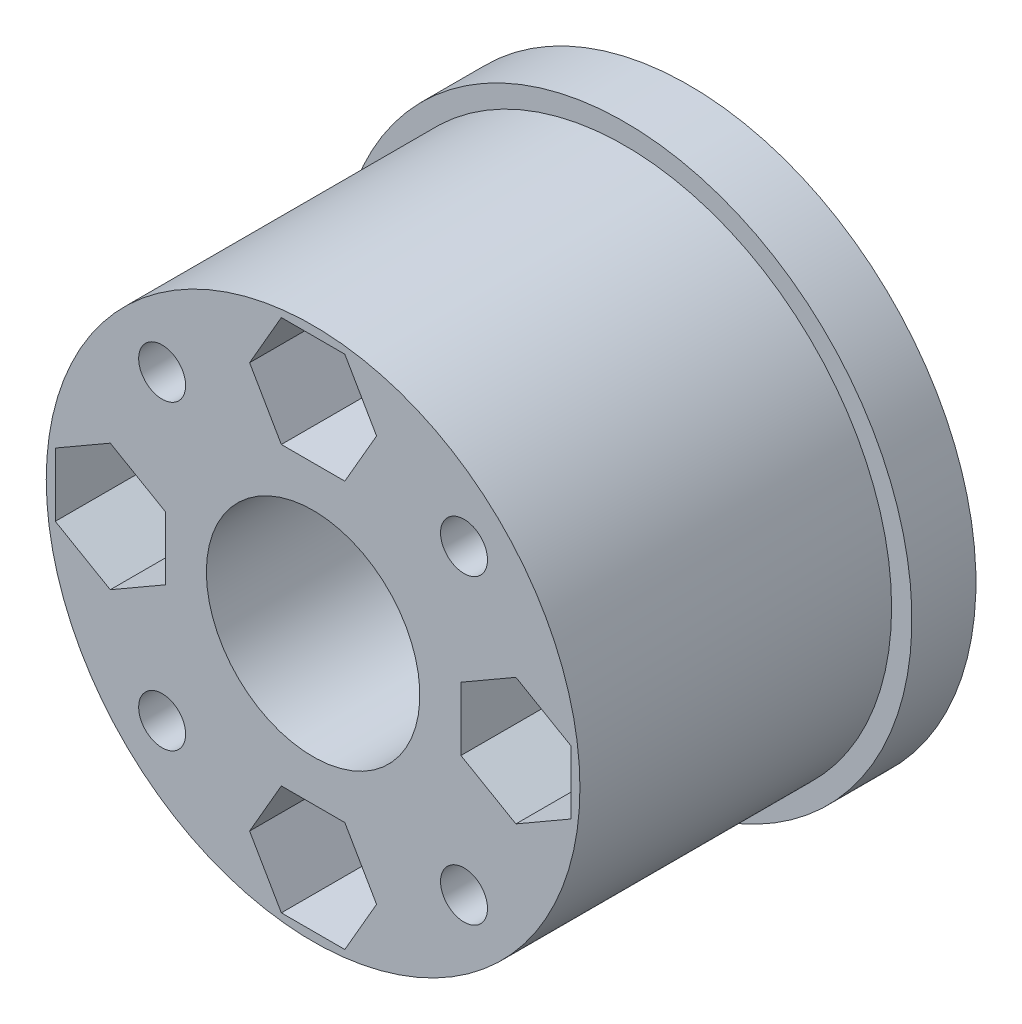
SolidWorks part; units mm, degrees
ref_plane "Front Plane" through (0, 0, 0) normal (0, 0, 1) x (1, 0, 0)
ref_plane "Top Plane" through (0, 0, 0) normal (0, 1, 0) x (1, 0, 0)
ref_plane "Right Plane" through (0, 0, 0) normal (1, 0, 0) x (0, 0, -1)
ref_axis "Z" through (0, 0, 15.48) along (0, 0, -1)
ref_plane "Plane1" through (0, 0, 0) normal (0.7071, 0.7071, 0) x (0, 0, -1)
sketch "Sketch10" plane through (0, 0, 0) normal (0, 1, 0) x (1, 0, 0)
  line L0 (-13.45, 3) -> (-7.5, 3)
  line L1 (0, 38.469) -> (0, 33.6342) construction
  line L2 (0, -15.48) -> (0, 3.88) construction
  line L3 (-13.45, 3) -> (-13.45, 0)
  line L4 (-13.45, 0) -> (-12.5, 0)
  line L5 (-12.5, 0) -> (-12.5, -14.6)
  line L10 (-12.5, -17.2) -> (-11, -17.2) construction
  line L11 (-11, -17.2) -> (-11, -16.2) construction
  line L12 (-11, -16.2) -> (-5, -16.2) construction
  line L14 (-7.5, 3) -> (-7.5, 2)
  line L15 (-7.5, 2) -> (-5, 2)
  line L18 (-5, 2) -> (-5, -14.6)
  line L19 (-12.5, -14.6) -> (-5, -14.6)
  line L20 (-5, -16.2) -> (-5, -14.6)
  line L21 (-12.5, -14.6) -> (-12.5, -17.2)
  dimension "D1" = 25
  dimension "D2" = 26.9
  dimension "D4" = 3
  dimension "D3" = 17.2
  dimension "D8" = 1
  dimension "D9" = 11
  dimension "D11" = 1
  dimension "D12" = 15
  dimension "D5" = 14.6
  dimension "D10" = 10
revolve "Revolve1" add sketch "Sketch10" angle 360 about L1
sketch "Sketch11" plane through (0, 0, 0) normal (0, 0, 1) x (1, 0, 0)
  line L0 (9.5, 0) -> (0, 0) construction
  circle A0 centre (9.5, 0) radius 1.325
  dimension "D2" = 2.65
  dimension "D1" = 9.5
extrude "AttachmentBoltHoles" cut sketch "Sketch11" against normal through all both and the other way through all
sketch "Sketch13" plane through (0, 0, -3) normal (0, 0, -1) x (-1, 0, 0)
  line L0 (-7.0711, 7.0711) -> (0, 0) construction
  line L1 (-9.5, 0) -> (0, 0) construction
  circle A0 centre (-7.0711, 7.0711) radius 1.975
  dimension "D2" = 3.95
  dimension "D1" = 45
  dimension "D3" = 10
extrude "ShaftBoltHead" cut sketch "Sketch13" against normal blind 2.2
sketch "Sketch14" plane through (0, 0, 0) normal (0, 0, 1) x (1, 0, 0)
  circle A0 centre (7.0711, 7.0711) radius 1.1
  dimension "D1" = 2.2
extrude "ShaftBoltThru" cut sketch "Sketch14" along normal through all both and the other way through all
sketch "Sketch12" plane through (0, 0, 14.6) normal (0, 0, 1) x (1, 0, 0)
  line L0 (9.5, 0) -> (0, 0) construction
  line L1 (12.075, -1.4867) -> (12.075, 1.4867)
  line L2 (12.075, 1.4867) -> (9.5, 2.9734)
  line L3 (9.5, 2.9734) -> (6.925, 1.4867)
  line L4 (6.925, 1.4867) -> (6.925, -1.4867)
  line L5 (6.925, -1.4867) -> (9.5, -2.9734)
  line L6 (9.5, -2.9734) -> (12.075, -1.4867)
  circle A0 centre (9.5, 0) radius 2.575 construction
  dimension "D1" = 5.15
extrude "NutHole" cut sketch "Sketch12" against normal offset from surface (12.6 mm away) 5 up to face at (5.0961, 7.0711, -3)
pattern_circular "CirPattern1" count 4 over 360 about axis through (0, 0, 15.48) along (0, 0, -1) of "AttachmentBoltHoles", "NutHole", "ShaftBoltThru", "ShaftBoltHead"
sketch "Sketch15" [suppressed] plane through (0, 0, 0) normal (0, 1, 0) x (1, 0, 0)
  line L0 (-4, -15) -> (-13.45, -15)
  line L1 (-12.5, -15) -> (-5, -15) construction
  line L2 (-13.45, -15) -> (-13.45, -17.6)
  line L3 (0, -10.5706) -> (0, -16.964) construction
  line L4 (-13.45, -17.6) -> (-5.45, -17.6)
  line L5 (-12.5, -17.6) -> (-11, -17.6) construction
  line L6 (-5.45, -17.6) -> (-5.45, -16.6)
  line L7 (-5.45, -16.6) -> (-4, -16.6)
  line L8 (-4, -16.6) -> (-4, -15)
  dimension "D1" = 26.9
  dimension "D2" = 10.9
  dimension "D3" = 1
  dimension "D4" = 8
revolve "Revolve2" [suppressed] add sketch "Sketch15" angle 360 about L3
sketch "Sketch16" [suppressed] plane through (0, 0, 17.6) normal (0, 0, 1) x (1, 0, 0)
  line L0 (7.0711, 7.0711) -> (0, 0) construction
  line L1 (5.3768, 8.7653) -> (4.7567, 6.4509)
  line L2 (4.7567, 6.4509) -> (6.4509, 4.7567)
  line L3 (6.4509, 4.7567) -> (8.7653, 5.3768)
  line L4 (8.7653, 5.3768) -> (9.3854, 7.6912)
  line L5 (9.3854, 7.6912) -> (7.6912, 9.3854)
  line L18 (7.6912, 9.3854) -> (5.3768, 8.7653)
  circle A0 centre (7.0711, 7.0711) radius 2.075 construction
  circle A1 centre (7.0711, 7.0711) radius 1.1
  circle A2 centre (7.0711, 7.0711) radius 1.1 construction
  dimension "D3" = 4.15
  dimension "D2" = 0
extrude "Cut-Extrude1" [suppressed] cut sketch "Sketch16" against normal blind 1.7
sketch "Sketch17" [suppressed] plane through (0, 0, 17.6) normal (0, 0, 1) x (1, 0, 0)
  line L6 (12.075, -1.4867) -> (12.075, 1.4867)
  line L7 (12.075, 1.4867) -> (9.5, 2.9734)
  line L8 (9.5, 2.9734) -> (6.925, 1.4867)
  line L9 (6.925, 1.4867) -> (6.925, -1.4867)
  line L10 (6.925, -1.4867) -> (9.5, -2.9734)
  line L11 (9.5, -2.9734) -> (12.075, -1.4867)
  line L12 (12.075, -1.4867) -> (12.075, 1.4867)
  line L13 (12.075, 1.4867) -> (9.5, 2.9734)
  line L14 (9.5, 2.9734) -> (6.925, 1.4867)
  line L15 (6.925, 1.4867) -> (6.925, -1.4867)
  line L16 (6.925, -1.4867) -> (9.5, -2.9734)
  line L17 (9.5, -2.9734) -> (12.075, -1.4867)
  circle A1 centre (7.0711, 7.0711) radius 1.1
  circle A2 centre (7.0711, 7.0711) radius 1.1
  dimension "D1" = 0
  dimension "D2" = 0
extrude "Cut-Extrude2" [suppressed] cut sketch "Sketch17" against normal through all both and the other way through all
pattern_circular "CirPattern2" [suppressed] count 4 over 360 about axis through (0, 0, 15.48) along (0, 0, -1) of bodies 125
equation "\"BearingOD\"= 32"
equation "\"BearingHeight\"= 4"
equation "\"SeatsOD\"= \"BearingOD\" + 10"
equation "\"RetainingRingThickness\" = 1.30"
equation "\"BearingBaseDistance\"= 17.2 - 2*\"BearingHeight\"  - \"RetainingRingThickness\"*2"
equation "\"WireHarnessHeight\"= 4"
equation "\"OuterWallWidth\"= 6"
equation "\"OverallOD\" = 43"
equation "\"RetaininRingGrooveDiameter\" = 23.9"
equation "\"ShaftLengthAfterFlange\" = 2*\"BearingHeight\" + \"BearingBaseDistance\" + \"RetainingRingThickness\"*2\t'give a retaining ring thickness of extra clearance"
equation "\"RetainingRingGrooveBase\" = \"ShaftLengthAfterFlange\" - \"RetainingRingThickness\"*2"
equation "\"BearingID\" = 25"
equation "\"CoverClearance\" = 1"
equation "\"CoverThickness\" = 1"
equation "\"FlangHeight\" = 3"
equation "\"OuterHousingHeight\" = \"WireHarnessHeight\" + \"BearingHeight\"*2 + \"BearingBaseDistance\""
equation "\"PCBWidth\" = 5"
equation "\"PCBHeight\" = \"OuterHousingHeight\" "
equation "\"PCBThickness\" = 1"
equation "\"NormalDistSidewallPCBToZ\" = (\"OverallOD\"/2) - 1.6\t'radial distance from the z axis to pcb origin on the top/connector side"
equation "\"PCBSidewallCutoutClearance\"= 0.1"
equation "\"OutputHubBoltCircleRadius\"= 8"
equation "\"OutputHubOD\"= 27"
equation "\"StatorWireRadius\"= \"NormalDistSidewallPCBToZ\" - 5.7"
equation "\"MountingHoleRadius\"= (\"OverallOD\"+\"BearingOD\")/4"
equation "\"D1@Sketch10\"=\"BearingID\""
equation "\"BearingInnerRaceOD\"= 26.9"
equation "\"D2@Sketch10\"=\"BearingInnerRaceOD\""
equation "\"D4@Sketch10\"=\"FlangHeight\""
equation "\"D3@Sketch10\"=\"ShaftLengthAfterFlange\""
equation "\"D1@Sketch11\"=round(\"BearingID\"*0.75)/2"
equation "\"D9@Sketch10\"=10.8+0.2"
equation "\"D5@Sketch10\"=\"BearingBaseDistance\" + \"BearingHeight\"*2"
equation "\"D10@Sketch10\"=10"
equation "\"D3@Sketch13\"=\"BearingID\"/2-2.5"
equation "\"D1@Sketch15\"=\"BearingInnerRaceOD\""
equation "\"D2@Sketch15\"=10.9"
